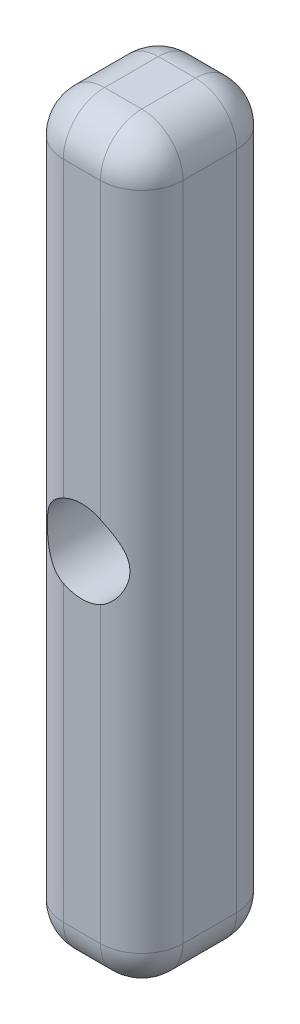
SolidWorks part; units mm, degrees
ref_plane "Front Plane" through (0, 0, 0) normal (1, 0, 0) x (0, 1, 0)
ref_plane "Top Plane" through (0, 0, 0) normal (0, 0, 1) x (0, 1, 0)
ref_plane "Right Plane" through (0, 0, 0) normal (0, 1, 0) x (-1, 0, 0)
sketch "Sketch7" plane through (0, 0, 0) normal (0, 0, 1) x (0, 1, 0)
  line L1 (-45, -7.25) -> (45, -7.25)
  line L2 (-45, -7.25) -> (-45, 7.25)
  line L3 (-45, 7.25) -> (45, 7.25)
  line L4 (45, -7.25) -> (45, 7.25)
  line L5 (-45, -7.25) -> (45, 7.25) construction
  line L6 (-45, 7.25) -> (45, -7.25) construction
  point P0 (0, 0)
  dimension "D1" = 14.5
  dimension "D2" = 90
extrude "Boss-Extrude1" add sketch "Sketch7" along normal blind 16.5
sketch "Sketch8" plane through (0, 0, 16.5) normal (0, 0, 1) x (0, -1, 0)
  circle A0 centre (0, 0) radius 5
  dimension "D1" = 10
extrude "Cut-Extrude2" cut sketch "Sketch8" against normal blind 13
fillet "Fillet1" radius 5 12 edges at (-7.25, 0, 16.5) (7.25, 0, 16.5) (7.25, 45, 8.25) (0, 45, 16.5) (-7.25, 45, 8.25) (-7.25, 0, 0) (7.25, 0, 0) (0, 45, 0) (-7.25, -45, 8.25) (0, -45, 16.5) (7.25, -45, 8.25) (0, -45, 0)
